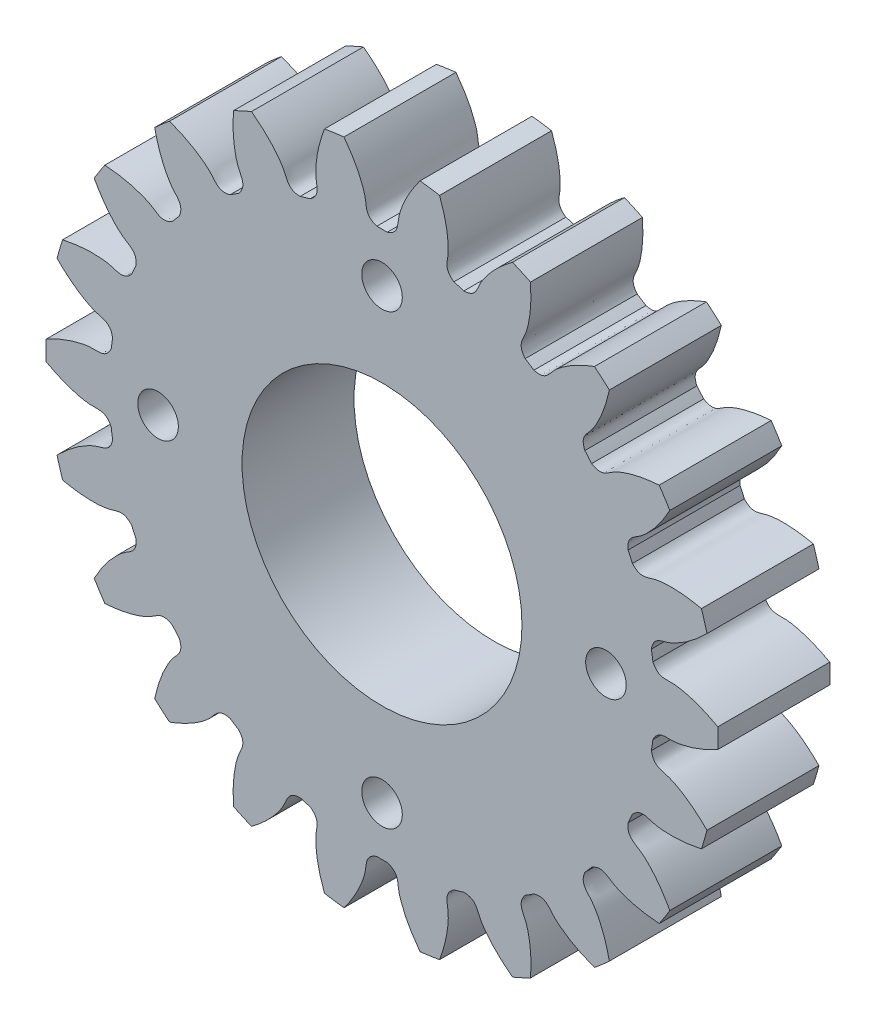
SolidWorks part; units mm, degrees
material "A-玻璃纤维"
ref_plane "前视基准面" through (0, 0, 0) normal (0, 0, 1) x (1, 0, 0)
ref_plane "上视基准面" through (0, 0, 0) normal (0, 1, 0) x (1, 0, 0)
ref_plane "右视基准面" through (0, 0, 0) normal (1, 0, 0) x (0, 0, -1)
other "Configuration Table"
sketch "草图1" plane through (0, 0, 0) normal (0, 0, 1) x (1, 0, 0)
  circle A0 centre (0, 0) radius 24
extrude "凸台-拉伸1" add sketch "草图1" along normal blind 8
ref_axis "基准轴1" through (0, 0, -0.25) along (0, 0, 1)
sketch "草图2" plane through (0, 0, 0) normal (0, 0, 1) x (1, 0, 0)
  line L0 (0, 0) -> (0, 24) construction
  circle A0 centre (0, 0) radius 24 construction
  arc A1 (0.3713, 19.4965) -> (-0.3713, 19.4965) centre (0, 0) ccw
  arc A2 (6.1711, 27.1197) -> (-6.1711, 27.1197) centre (0, 0) ccw
  spline S0 degree 3 poles (0.3713, 19.4965) (1.1763, 19.7524) (1.0967, 20.3035) (1.1992, 20.8431) (1.2119, 20.9038) (1.2278, 20.9723) (1.247, 21.0485) (1.2699, 21.1323) (1.2968, 21.2235) (1.328, 21.322) (1.3639, 21.4277) (1.4047, 21.5405) (1.4506, 21.6602) (1.5021, 21.7865) (1.5594, 21.9194) (1.6227, 22.0587) (1.6924, 22.2041) (1.7687, 22.3555) (1.8519, 22.5127) (1.9422, 22.6753) (2.0399, 22.8433) (2.1452, 23.0164) (2.2584, 23.1943) (2.3798, 23.3768) (2.5094, 23.5636) (2.6477, 23.7545) (2.7947, 23.9492) (2.9506, 24.1474) (3.1158, 24.3489) (3.2903, 24.5533) (3.4744, 24.7603) (3.6682, 24.9697) (3.8718, 25.1812) (4.0856, 25.3943) (4.3095, 25.6089) (4.5437, 25.8245) (4.7884, 26.0409) (5.0437, 26.2577) (5.3096, 26.4746) (5.683, 26.7669) (5.9729, 26.9799) (6.1711, 27.1197) knots 0 0 0 0 0.157021 0.162531 0.168888 0.176093 0.184146 0.193046 0.202794 0.213389 0.224833 0.237123 0.250262 0.264248 0.279082 0.294763 0.311292 0.328669 0.346893 0.365965 0.385884 0.406652 0.428266 0.450729 0.474039 0.498197 0.523202 0.549055 0.575756 0.603304 0.6317 0.660944 0.691035 0.721974 0.75376 0.786395 0.819876 0.854206 0.889383 0.925408 1 1 1 1
  spline S1 degree 3 poles (-0.3713, 19.4965) (-1.1763, 19.7524) (-1.0967, 20.3035) (-1.1992, 20.8431) (-1.2119, 20.9038) (-1.2278, 20.9723) (-1.247, 21.0485) (-1.2699, 21.1323) (-1.2968, 21.2235) (-1.328, 21.322) (-1.3639, 21.4277) (-1.4047, 21.5405) (-1.4506, 21.6602) (-1.5021, 21.7865) (-1.5594, 21.9194) (-1.6227, 22.0587) (-1.6924, 22.2041) (-1.7687, 22.3555) (-1.8519, 22.5127) (-1.9422, 22.6753) (-2.0399, 22.8433) (-2.1452, 23.0164) (-2.2584, 23.1943) (-2.3798, 23.3768) (-2.5094, 23.5636) (-2.6477, 23.7545) (-2.7947, 23.9492) (-2.9506, 24.1474) (-3.1158, 24.3489) (-3.2903, 24.5533) (-3.4744, 24.7603) (-3.6682, 24.9697) (-3.8718, 25.1812) (-4.0856, 25.3943) (-4.3095, 25.6089) (-4.5437, 25.8245) (-4.7884, 26.0409) (-5.0437, 26.2577) (-5.3096, 26.4746) (-5.683, 26.7669) (-5.9729, 26.9799) (-6.1711, 27.1197) knots 0 0 0 0 0.157021 0.162531 0.168888 0.176093 0.184146 0.193046 0.202794 0.213389 0.224833 0.237123 0.250262 0.264248 0.279082 0.294763 0.311292 0.328669 0.346893 0.365965 0.385884 0.406652 0.428266 0.450729 0.474039 0.498197 0.523202 0.549055 0.575756 0.603304 0.6317 0.660944 0.691035 0.721974 0.75376 0.786395 0.819876 0.854206 0.889383 0.925408 1 1 1 1
extrude "切除-拉伸1" cut sketch "草图2" along normal through all
pattern_circular "阵列(圆周)1" count 22 every 16.364 about axis through (0, 0, -0.25) along (0, 0, 1) of "切除-拉伸1"
sketch "草图3" plane through (0, 0, 0) normal (0, 0, 1) x (1, 0, 0)
  circle A0 centre (0, 0) radius 22 construction
  dimension "Dn" = 44
sketch "草图4" plane through (0, 0, 8) normal (0, 0, 1) x (1, 0, 0)
  circle A0 centre (0, 0) radius 16 construction
  circle A1 centre (0, 16) radius 1.45
  circle A2 centre (16, 0) radius 1.45
  circle A3 centre (0, -16) radius 1.45
  circle A4 centre (-16, 0) radius 1.45
  dimension "D1" = 32
  dimension "D2" = 2.9
extrude "切除-拉伸2" cut sketch "草图4" against normal through all
sketch "草图5" plane through (0, 0, 8) normal (0, 0, 1) x (1, 0, 0)
  circle A0 centre (0, 0) radius 10
  dimension "D1" = 20
extrude "切除-拉伸3" cut sketch "草图5" against normal through all
